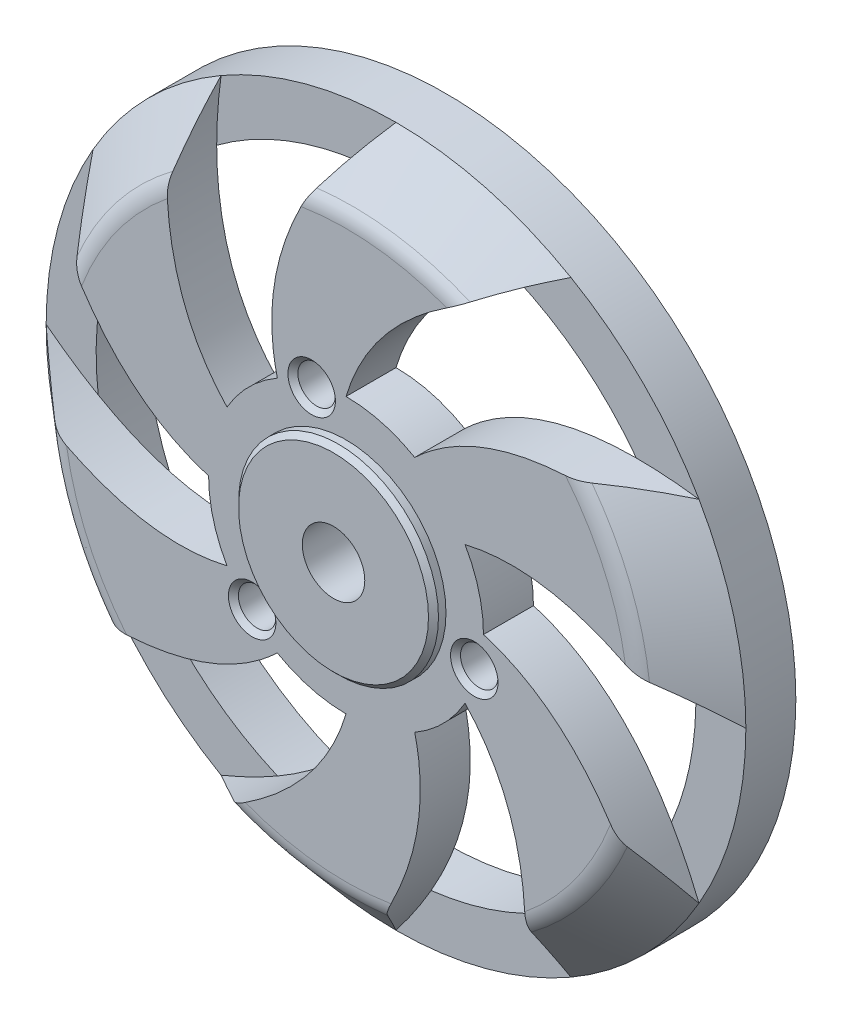
SolidWorks part; units mm, degrees
ref_plane "Front Plane" through (0, 0, 0) normal (0, 0, 1) x (1, 0, 0)
ref_plane "Top Plane" through (0, 0, 0) normal (0, 1, 0) x (1, 0, 0)
ref_plane "Right Plane" through (0, 0, 0) normal (1, 0, 0) x (0, 0, -1)
sketch "Sketch1" plane through (0, 0, 0) normal (0, 0, 1) x (1, 0, 0)
  circle A0 centre (0, 0) radius 14
  circle A1 centre (0, 0) radius 12
extrude "Boss-Extrude1" add sketch "Sketch1" along normal blind 2
sketch "Sketch2" plane through (0, 0, 2) normal (0, 0, 1) x (1, 0, 0)
  line L2 (2.75, 4.7631) -> (7, 12.1244) construction
  arc A0 (-2.75, 4.7631) -> (-4.7631, 2.75) centre (0, 0) ccw
  arc A1 (-7, 12.1244) -> (-12.1244, 7) centre (0, 0) ccw
  arc A2 (-5.5, 0) -> (-4.7631, -2.75) centre (0, 0) ccw
  arc A3 (-2.75, -4.7631) -> (0, -5.5) centre (0, 0) ccw
  arc A4 (2.75, -4.7631) -> (4.7631, -2.75) centre (0, 0) ccw
  arc A5 (5.5, 0) -> (4.7631, 2.75) centre (0, 0) ccw
  arc A6 (2.75, 4.7631) -> (0, 5.5) centre (0, 0) ccw
  arc A7 (-14, 0) -> (-12.1244, -7) centre (0, 0) ccw
  arc A8 (-7, -12.1244) -> (0, -14) centre (0, 0) ccw
  arc A9 (7, -12.1244) -> (12.1244, -7) centre (0, 0) ccw
  arc A10 (14, 0) -> (12.1244, 7) centre (0, 0) ccw
  arc A11 (7, 12.1244) -> (0, 14) centre (0, 0) ccw
  spline S0 degree 2 poles (0, 5.5) (1.2717, 9.7714) (7, 12.1244) knots 0.363335 0.363335 0.363335 1 1 1
  spline S1 degree 2 poles (-2.75, 4.7631) (-3.7844, 9.0981) (0, 14) knots 0.363335 0.363335 0.363335 1 1 1
  spline S2 degree 2 poles (4.7631, 2.75) (9.0981, 3.7844) (14, 0) knots 0.363335 0.363335 0.363335 1 1 1
  spline S3 degree 2 poles (2.75, 4.7631) (5.987, 7.8264) (12.1244, 7) knots 0.363335 0.363335 0.363335 1 1 1
  spline S4 degree 2 poles (4.7631, -2.75) (7.8264, -5.987) (7, -12.1244) knots 0.363335 0.363335 0.363335 1 1 1
  spline S5 degree 2 poles (5.5, 0) (9.7714, -1.2717) (12.1244, -7) knots 0.363335 0.363335 0.363335 1 1 1
  spline S6 degree 2 poles (0, -5.5) (-1.2717, -9.7714) (-7, -12.1244) knots 0.363335 0.363335 0.363335 1 1 1
  spline S7 degree 2 poles (2.75, -4.7631) (3.7844, -9.0981) (0, -14) knots 0.363335 0.363335 0.363335 1 1 1
  spline S8 degree 2 poles (-4.7631, -2.75) (-9.0981, -3.7844) (-14, 0) knots 0.363335 0.363335 0.363335 1 1 1
  spline S9 degree 2 poles (-2.75, -4.7631) (-5.987, -7.8264) (-12.1244, -7) knots 0.363335 0.363335 0.363335 1 1 1
  spline S10 degree 2 poles (-4.7631, 2.75) (-7.8264, 5.987) (-7, 12.1244) knots 0.363335 0.363335 0.363335 1 1 1
  spline S11 degree 2 poles (-5.5, 0) (-9.7714, 1.2717) (-12.1244, 7) knots 0.363335 0.363335 0.363335 1 1 1
extrude "Boss-Extrude2" add sketch "Sketch2" along normal blind 2
chamfer "Chamfer1" distance 2 angle 49 6 edges at (-9.8995, 9.8995, 4) (-13.523, -3.6235, 4) (-3.6235, -13.523, 4) (9.8995, -9.8995, 4) (13.523, 3.6235, 4) (3.6235, 13.523, 4) first distance on face at (0, 0, 3)
fillet "Fillet1" radius 1 6 edges at (10.7852, 4.5333, 4) (9.3186, -7.0736, 4) (-1.4666, -11.607, 4) (-10.7852, -4.5333, 4) (-9.3186, 7.0736, 4) (1.4666, 11.607, 4)
sketch "Sketch3" plane through (0, 0, 4) normal (0, 0, 1) x (1, 0, 0)
  circle A0 centre (0, 0) radius 4
extrude "Boss-Extrude3" add sketch "Sketch3" along normal blind 0.5
chamfer "Chamfer2" distance 0.2 angle 45 1 edges at (4, 0, 4.5)
sketch "Sketch4" plane through (0, 0, 4) normal (0, 0, 1) x (1, 0, 0)
  line L0 (0, 5.5) -> (-2.75, 4.7631) construction
  line L1 (0, 0) -> (-1.375, 5.1316) construction
  circle A1 centre (-1.375, 5.1316) radius 0.75
  circle A2 centre (5.1316, -1.375) radius 0.75
  circle A3 centre (-3.7566, -3.7566) radius 0.75
  dimension "D1" = 3
extrude "Cut-Extrude1" cut sketch "Sketch4" against normal up to next
chamfer "Chamfer3" distance 0.2 angle 45 3 edges at (-3.0066, -3.7566, 4) (5.8816, -1.375, 4) (-0.625, 5.1316, 4)
sketch "Sketch5" plane through (0, 0, 4.5) normal (0, 0, 1) x (1, 0, 0)
  circle A0 centre (0, 0) radius 1.25
extrude "Cut-Extrude2" cut sketch "Sketch5" against normal blind 10
